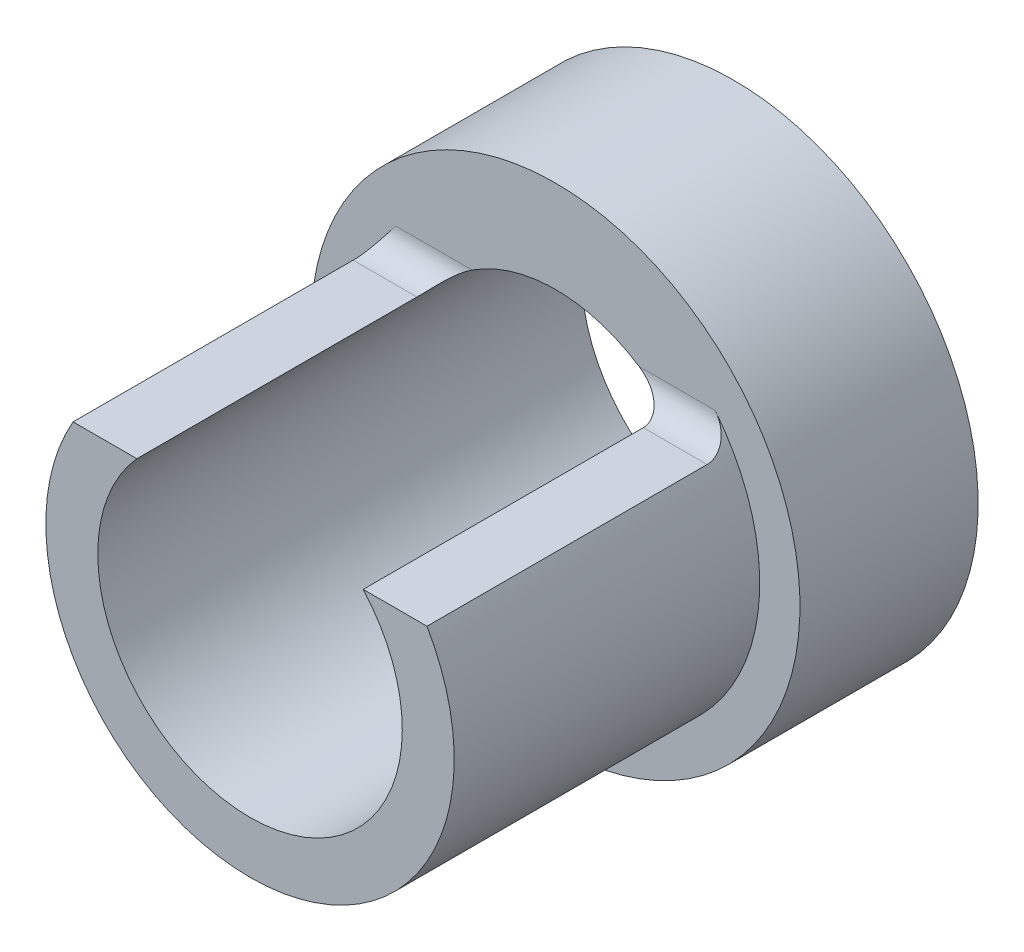
SolidWorks part; units mm, degrees
ref_plane "Front Plane" through (0, 0, 0) normal (0, 0, 1) x (1, 0, 0)
ref_plane "Top Plane" through (0, 0, 0) normal (0, 1, 0) x (1, 0, 0)
ref_plane "Right Plane" through (0, 0, 0) normal (1, 0, 0) x (0, 0, -1)
sketch "Sketch1" plane through (0, 0, 0) normal (0, 0, 1) x (1, 0, 0)
  line L0 (-1.7378, 1) -> (-1.1113, 1)
  line L1 (1.1113, 1) -> (1.7378, 1)
  arc A0 (-1.1113, 1) -> (1.1113, 1) centre (0, 0) ccw
  arc A1 (-1.7378, 1) -> (1.7378, 1) centre (0, 0) ccw
  circle A2 centre (0, 0) radius 2.005 construction
  circle A3 centre (0, 0) radius 1.495 construction
  dimension "D1" = 2.99
  dimension "D3" = 1
  dimension "D2" = 0.51
extrude "Boss-Extrude1" add sketch "Sketch1" along normal blind 3
sketch "Sketch2" plane through (0, 0, 0) normal (0, 0, -1) x (-1, 0, 0)
  circle A0 centre (0, 0) radius 1.495
  arc A1 (-1.1113, 1) -> (1.1113, 1) centre (0, 0) ccw construction
  circle A2 centre (0, 0) radius 2.4
  dimension "D1" = 4.8
extrude "Boss-Extrude2" add sketch "Sketch2" along normal blind 1.75
fillet "Fillet1" radius 0.25 2 edges at (-1.4246, 1, 0) (1.4246, 1, 0)
